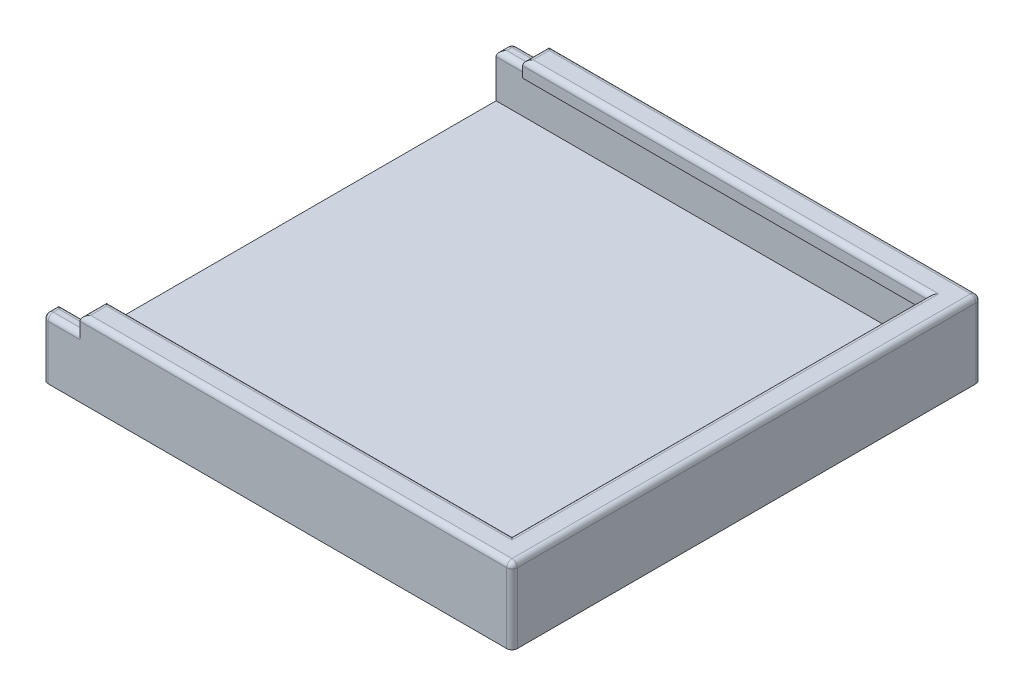
SolidWorks part; units mm, degrees
note: The reader was unsure of these and kept them because the rebuilt part matched: shared geometry of "Sketch2<3>".
ref_plane "Front Plane" through (0, 0, 0) normal (0, 0, 1) x (1, 0, 0)
ref_plane "Top Plane" through (0, 0, 0) normal (0, 1, 0) x (1, 0, 0)
ref_plane "Right Plane" through (0, 0, 0) normal (1, 0, 0) x (0, 0, -1)
sketch "Board Outline" plane through (0, 0, 0) normal (0, 1, 0) x (1, 0, 0)
  line L1 (-20.3, 20.3) -> (20.3, 20.3)
  line L2 (-20.3, 20.3) -> (-20.3, -20.3)
  line L3 (-20.3, -20.3) -> (20.3, -20.3)
  line L4 (20.3, 20.3) -> (20.3, -20.3)
  line L5 (-20.3, 20.3) -> (20.3, -20.3) construction
  line L6 (-20.3, -20.3) -> (20.3, 20.3) construction
  point P0 (0, 0)
  dimension "D1" = 40.6
sketch "Sketch2" plane through (0, 0, 0) normal (0, 1, 0) x (1, 0, 0)
  line L0 (20.3, 20.3) -> (20.3, -20.3) construction
  line L1 (-22.1, 22.1) -> (22.1, 22.1)
  line L2 (-22.1, 22.1) -> (-22.1, -22.1)
  line L3 (-22.1, -22.1) -> (22.1, -22.1)
  line L4 (22.1, 22.1) -> (22.1, -22.1)
  line L5 (-22.1, 22.1) -> (22.1, -22.1) construction
  line L6 (-22.1, -22.1) -> (22.1, 22.1) construction
  line L8 (-20.6, 20.6) -> (20.6, 20.6)
  line L9 (-20.6, 20.6) -> (-20.6, -20.6)
  line L10 (-20.6, -20.6) -> (20.6, -20.6)
  line L11 (20.6, 20.6) -> (20.6, -20.6)
  line L12 (-20.6, 20.6) -> (20.6, -20.6) construction
  line L13 (-20.6, -20.6) -> (20.6, 20.6) construction
  point P0 (0, 0)
  point P8 (0, 0)
  dimension "D1" = 1.5
  dimension "D2" = 0.3
extrude "Boss-Extrude1" add sketch "Sketch2" against normal blind 1.5 contours L4 L3 L2 L1
extrude "Boss-Extrude2" add sketch "Sketch2<3>" along normal blind 4.1 contours L2 L3 L4 L1
sketch "Sketch2<3>" plane through (0, 0, 0) normal (0, 1, 0) x (1, 0, 0) same geometry as "Sketch2"
sketch "Sketch3" plane through (0, 4.1, 0) normal (0, 1, 0) x (1, 0, 0)
  line L0 (-22.1, -22.1) -> (22.1, -22.1) construction
  line L1 (22.1, 22.1) -> (19.6, 22.1)
  line L2 (22.1, 22.1) -> (22.1, -22.1)
  line L3 (22.1, -22.1) -> (19.6, -22.1)
  line L4 (19.6, 22.1) -> (19.6, -22.1)
  line L5 (20.6, -20.6) -> (20.6, 20.6) construction
  dimension "D1" = 1
extrude "Boss-Extrude3" add sketch "Sketch3" along normal blind 1.5
sketch "Sketch6" plane through (19.6, 0, 0) normal (-1, 0, 0) x (0, 0, 1)
  line L0 (-19.6, 5.6) -> (-19.6, 4.1)
  line L1 (19.6, 5.6) -> (19.6, 4.1)
  line L2 (-19.6, 5.6) -> (-22.1, 5.6)
  line L3 (19.6, 4.1) -> (20.6, 4.1)
  line L6 (-22.1, 4.1) -> (-20.6, 4.1)
  line L7 (-20.6, 4.1) -> (20.6, 4.1)
  line L8 (20.6, 4.1) -> (22.1, 4.1)
  line L9 (22.1, 4.1) -> (22.1, 5.6)
  line L10 (22.1, 5.6) -> (-22.1, 5.6)
  line L11 (-22.1, 5.6) -> (-22.1, 4.1)
  line L12 (-22.1, 4.1) -> (-20.6, 4.1)
  line L13 (-20.6, 4.1) -> (-19.6, 4.1)
  line L14 (20.6, 4.1) -> (22.1, 4.1)
  line L15 (22.1, 4.1) -> (22.1, 5.6)
  line L16 (22.1, 5.6) -> (19.6, 5.6)
  line L17 (-22.1, 5.6) -> (-22.1, 4.1)
  dimension "D2" = 2.5
  dimension "D3" = 2.5
  dimension "D1" = 0
extrude "Boss-Extrude5" add sketch "Sketch6" along normal offset from surface (38.2 mm away) 2 up to face at (-20.6, 2.05, 0)
sketch "Sketch5" plane through (0, 4.1, 0) normal (0, 1, 0) x (1, 0, 0)
  line L1 (-20.6, 20.6) -> (-27.1465, 20.6)
  line L2 (-20.6, 20.6) -> (-20.6, -20.6)
  line L3 (-20.6, -20.6) -> (-27.1465, -20.6)
  line L4 (-27.1465, 20.6) -> (-27.1465, -20.6)
extrude "Cut-Extrude1" cut sketch "Sketch5" against normal up to surface (4.1 mm away) up to face at (0, 0, 0)
fillet "Fillet2" radius 0.5 18 edges at (-22.1, 1.3, -22.1) (-22.1, 1.3, 22.1) (1.75, 5.6, -22.1) (22.1, 2.05, -22.1) (22.1, 2.05, 22.1) (22.1, 5.6, 0) (1.75, 5.6, 22.1) (-22.1, 4.1, 21.35) (-20.35, 4.1, 22.1) (-20.35, 4.1, 20.6) (-22.1, 4.1, -21.35) (-20.35, 4.1, -22.1) (-20.35, 4.1, -20.6) (19.6, 5.6, 0) (0.5, 5.6, 19.6) (0.5, 5.6, -19.6) (-18.6, 5.6, 20.85) (-18.6, 5.6, -20.85)
